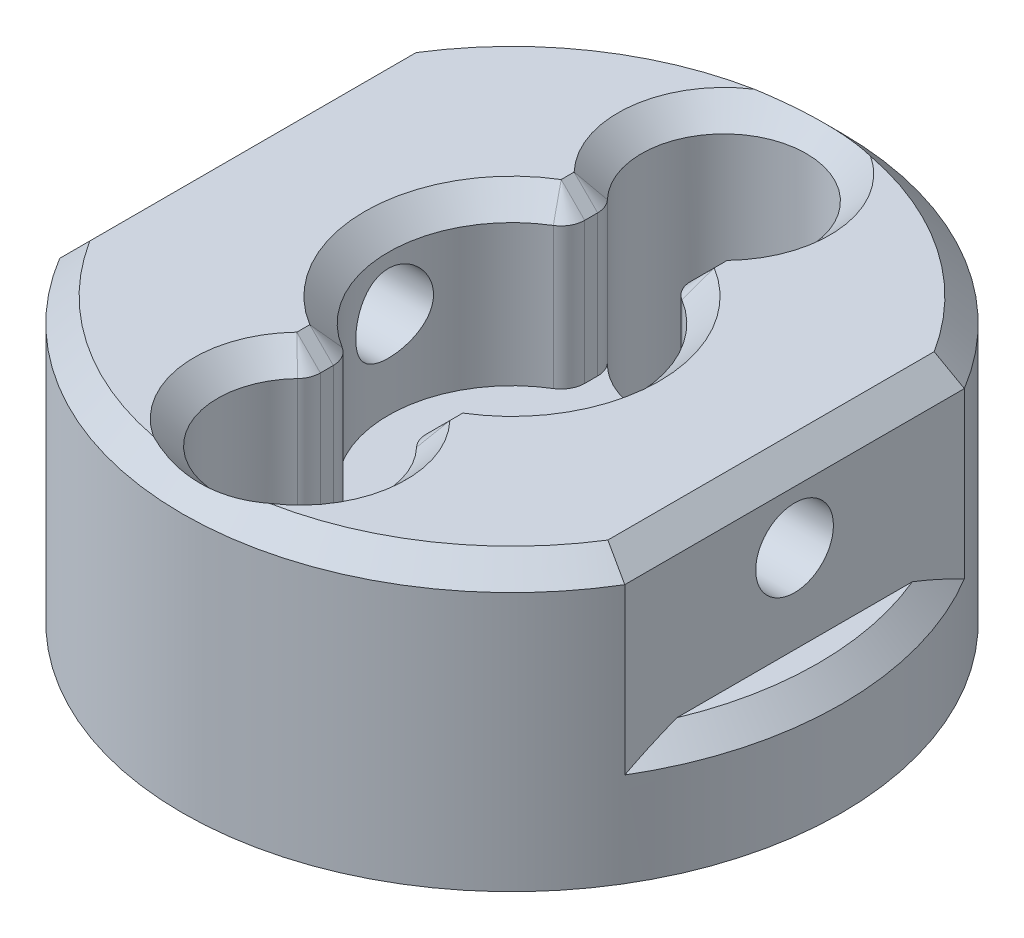
SolidWorks part; units mm, degrees
ref_plane "Front Plane" through (0, 0, 0) normal (0, 0, 1) x (1, 0, 0)
ref_plane "Top Plane" through (0, 0, 0) normal (0, 1, 0) x (1, 0, 0)
ref_plane "Right Plane" through (0, 0, 0) normal (1, 0, 0) x (0, 0, -1)
sketch "Sketch1" plane through (0, 0, 0) normal (0, 1, 0) x (1, 0, 0)
  circle A0 centre (0, 0) radius 14
  circle A1 centre (0, 0) radius 2.25
  dimension "D1" = 28
  dimension "D2" = 4.5
extrude "Boss-Extrude1" add sketch "Sketch1" along normal blind 5
sketch "Sketch2" plane through (0, 5, 0) normal (0, 1, 0) x (1, 0, 0)
  line L0 (0, -1000) -> (0, 49000) construction
  line L1 (-1000, 0) -> (49000, 0) construction
  line L2 (4.2426, 4.2426) -> (0, 0) construction
  circle A0 centre (0, 9) radius 1.5
  circle A1 centre (4.2426, 4.2426) radius 1.5 construction
  dimension "D1" = 3
  dimension "D2" = 3
  dimension "D3" = 9
  dimension "D4" = 6
  dimension "D5" = 45
extrude "Cut-Extrude1" cut sketch "Sketch2" against normal through all
sketch "Sketch4" plane through (0, 5, 0) normal (0, 1, 0) x (1, 0, 0)
  circle A0 centre (0, 9) radius 3.5
  dimension "D1" = 7
extrude "Cut-Extrude2" cut sketch "Sketch4" against normal blind 3
pattern_circular "CirPattern1" count 2 over 360 about axis through (0, 5, 0) along (0, -1, 0) of "Cut-Extrude1", "Cut-Extrude2" reverse direction yes
sketch "Sketch5" plane through (0, 5, 0) normal (0, 1, 0) x (1, 0, 0)
  circle A0 centre (0, 0) radius 5.25
  circle A1 centre (0, 0) radius 14
  circle A2 centre (0, 0) radius 14 construction
  dimension "D1" = 10.5
extrude "Boss-Extrude2" add sketch "Sketch5" along normal blind 7
sketch "Sketch6" plane through (0, 5, 0) normal (0, 1, 0) x (1, 0, 0)
  circle A2 centre (0, 9) radius 3.5 construction
  circle A3 centre (0, -9) radius 3.5 construction
  circle A6 centre (0, 9) radius 3.5
  circle A7 centre (0, -9) radius 3.5
extrude "Cut-Extrude3" cut sketch "Sketch6" along normal through all
sketch "Sketch9" plane through (0, 12, 0) normal (0, 1, 0) x (1, 0, 0)
  line L1 (12, -15) -> (-12, -15)
  line L2 (12, -15) -> (12, 15)
  line L3 (12, 15) -> (-12, 15)
  line L4 (-12, -15) -> (-12, 15)
  line L5 (12, -15) -> (-12, 15) construction
  line L6 (12, 15) -> (-12, -15) construction
  point P0 (0, 0)
  dimension "D1" = 12
  dimension "D2" = 30
extrude "Cut-Extrude5" cut sketch "Sketch9" against normal up to surface (7 mm away) flip side to cut up to face at (0, 5, 2.25)
ref_axis "Axis1" through (0, 12, 0) along (0, -1, 0)
sketch "Sketch10" plane through (12, 0, 0) normal (1, 0, 0) x (0, 0, -1)
  line L0 (7.2111, 5) -> (-7.2111, 5) construction
  circle A0 centre (0, 8.75) radius 1.65
  point P4 (5.7644, 8.75)
  dimension "D2" = 3.3
  dimension "D1" = 3.75
extrude "Cut-Extrude6" cut sketch "Sketch10" against normal through all
sketch "Sketch12" plane through (0, 12, 0) normal (0, 1, 0) x (1, 0, 0)
  line L1 (2.25, -9) -> (-2.25, -9)
  line L2 (2.25, -9) -> (2.25, 9)
  line L3 (2.25, 9) -> (-2.25, 9)
  line L4 (-2.25, -9) -> (-2.25, 9)
  line L5 (2.25, -9) -> (-2.25, 9) construction
  line L6 (2.25, 9) -> (-2.25, -9) construction
  circle A0 centre (0, 0) radius 2.25 construction
  point P0 (0, 0)
  point P6 (0, 9)
extrude "Cut-Extrude7" cut sketch "Sketch12" against normal up to surface (7 mm away) up to face at (0, 5, 2.25)
chamfer "Chamfer2" distance 0.4 angle 85 1 edges at (0, 5, 2.25) first distance on face at (0, 5, 2.25)
fillet "Fillet2" radius 1 8 edges at (2.25, 8.5, 6.319) (2.25, 8.5, 4.7434) (2.25, 8.5, -4.7434) (2.25, 8.5, -6.319) (-2.25, 8.5, -6.319) (-2.25, 8.5, -4.7434) (-2.25, 8.5, 4.7434) (-2.25, 8.5, 6.319)
chamfer "Chamfer3" distance 1 angle 45 22 edges at (-14, 5, 0) (14, 5, 0) (12, 12, 0) (0, 12, -14) (-12, 12, 0) (0, 12, 14) (5.25, 12, 0) (2.3782, 12, -4.8486) (2.3782, 12, 4.8486) (2.25, 12, -5.613) (2.25, 12, 5.613) (2.322, 12, -6.2602) (2.322, 12, 6.2602) (0, 12, -12.5) (0, 12, 12.5) (-2.322, 12, -6.2602) (-2.322, 12, 6.2602) (-2.25, 12, -5.613) (-2.25, 12, 5.613) (-2.3782, 12, -4.8486) (-2.3782, 12, 4.8486) (-5.25, 12, 0)
